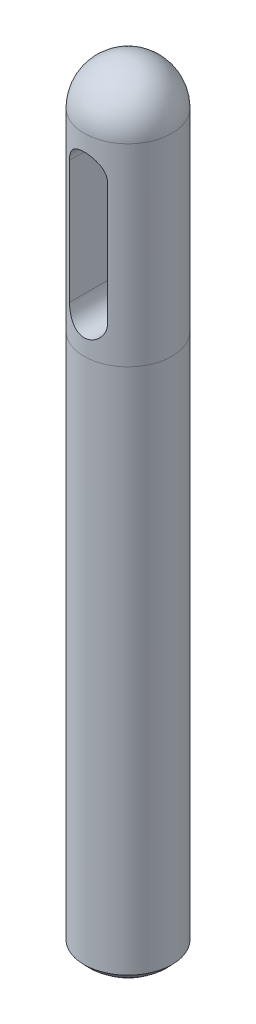
SolidWorks part; units mm, degrees
ref_plane "Front Plane" through (0, 0, 0) normal (0, 0, 1) x (1, 0, 0)
ref_plane "Top Plane" through (0, 0, 0) normal (0, 1, 0) x (1, 0, 0)
ref_plane "Right Plane" through (0, 0, 0) normal (1, 0, 0) x (0, 0, -1)
sketch "Szkic2" plane through (0, 0, 0) normal (0, 1, 0) x (1, 0, 0)
  circle A0 centre (0, 0) radius 2.5
  dimension "D1" = 5
extrude "Dodanie-wyciągnięcie1" add sketch "Szkic2" along normal blind 30 contours A0
sketch "Szkic3" plane through (0, 0, 0) normal (0, 0, 1) x (1, 0, 0)
  line L0 (0, 0) -> (0, 30)
  line L1 (2.5, 30) -> (-2.5, 30) construction
  line L2 (0, 30) -> (-2.5, 30)
  line L3 (0, 30) -> (0, 32)
  line L4 (0, 32) -> (0, 39)
  line L5 (0, 39) -> (0, 28.5886)
  line L6 (0, 39) -> (0, 41)
  line L7 (0, 32) -> (0, 39) construction
  line L8 (-1.0816, 32) -> (-1.0816, 39)
  line L9 (1.0816, 32) -> (1.0816, 39)
  line L10 (0, 41) -> (0, 30) construction
  line L11 (2.4977, 41) -> (2.4977, 30)
  line L12 (-2.4977, 41) -> (-2.4977, 30)
  line L13 (0, 40) -> (0, 43.4977)
  line L14 (0, 43.4977) -> (0, 27.5023)
  arc A0 (-1.0816, 32) -> (1.0816, 32) centre (0, 32) ccw
  arc A1 (1.0816, 39) -> (-1.0816, 39) centre (0, 39) ccw
  arc A2 (2.4977, 41) -> (-2.4977, 41) centre (0, 41) ccw
  arc A3 (-2.4977, 30) -> (2.4977, 30) centre (0, 30) ccw
  point P7 (0, 35.5)
  point P16 (0, 35.5)
  dimension "D1" = 7
  dimension "D2" = 2
  dimension "D3" = 2
revolve "Obrót2" add sketch "Szkic3" angle 360 about L0 region at (-1.5052, 36.8996, 0) region at (-0.5248, 35.5, 0)
extrude "Wytnij-wyciągnięcie1" cut sketch "Szkic3<3>" against normal blind 20 and the other way blind 20 contours L6 A1 L8 A0 L14 L4 | L9 A1 L6 L4 L14 A0 region at (-0.5248, 35.5, 0) region at (0.5248, 35.5, 0)
sketch "Szkic3<3>" plane through (0, 0, 0) normal (0, 0, 1) x (1, 0, 0) same geometry as "Szkic3"
sketch "Szkic4" plane through (0, 0, 0) normal (0, 0, 1) x (1, 0, 0)
  line L0 (0, -1.179) -> (0, 0)
  line L1 (-2.5, 0) -> (2.5, 0)
  arc A0 (-2.5, 0) -> (2.5, 0) centre (0, 2.0611) ccw
revolve "Obrót3" add sketch "Szkic4" angle 360 about L0 region at (-0.9653, -0.4798, 0)
